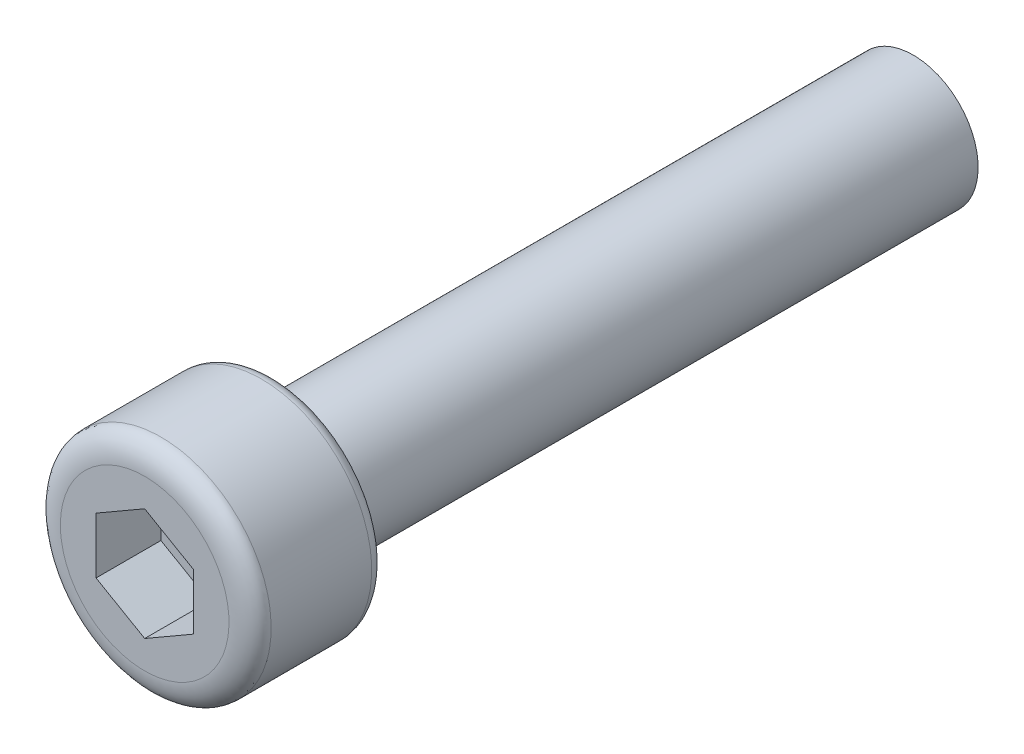
SolidWorks part; units mm, degrees
ref_plane "前视基准面" through (0, 0, 0) normal (0, 0, 1) x (1, 0, 0)
ref_plane "上视基准面" through (0, 0, 0) normal (0, 1, 0) x (1, 0, 0)
ref_plane "右视基准面" through (0, 0, 0) normal (1, 0, 0) x (0, 0, -1)
sketch "草图2" plane through (0, 0, 0) normal (1, 0, 0) x (0, 0, -1)
  line L0 (-12, 0) -> (-12, 3.4)
  line L1 (-12, 3.4) -> (-8, 3.4)
  line L2 (-8, 3.4) -> (-8, 2)
  line L3 (-8, 2) -> (12, 2)
  line L4 (12, 2) -> (12, 0)
  line L5 (12, 0) -> (-12, 0)
  dimension "D1" = 20
  dimension "D2" = 3.4
  dimension "D3" = 2
  dimension "D4" = 4
revolve "旋转1" add sketch "草图2" angle 360 about L5
chamfer "倒角1" distance 0.3 angle 60 1 edges at (-2, 0, -12) first distance on face at (-2, 0, 8)
fillet "圆角1" radius 0.4 1 edges at (-3.4, 0, 8)
fillet "圆角2" radius 0.8 1 edges at (-3.4, 0, 12) second distance 0.5 first distance on face at (-3.4, 0, 12)
sketch "草图3" plane through (0, 0, 12) normal (0, 0, 1) x (1, 0, 0)
  line L1 (0, 1.7321) -> (-1.5, 0.866)
  line L2 (-1.5, 0.866) -> (-1.5, -0.866)
  line L3 (-1.5, -0.866) -> (0, -1.7321)
  line L4 (0, -1.7321) -> (1.5, -0.866)
  line L5 (1.5, -0.866) -> (1.5, 0.866)
  line L6 (1.5, 0.866) -> (0, 1.7321)
  circle A0 centre (0, 0) radius 1.5 construction
  dimension "D1" = 3
extrude "切除-拉伸1" cut sketch "草图3" against normal blind 2
